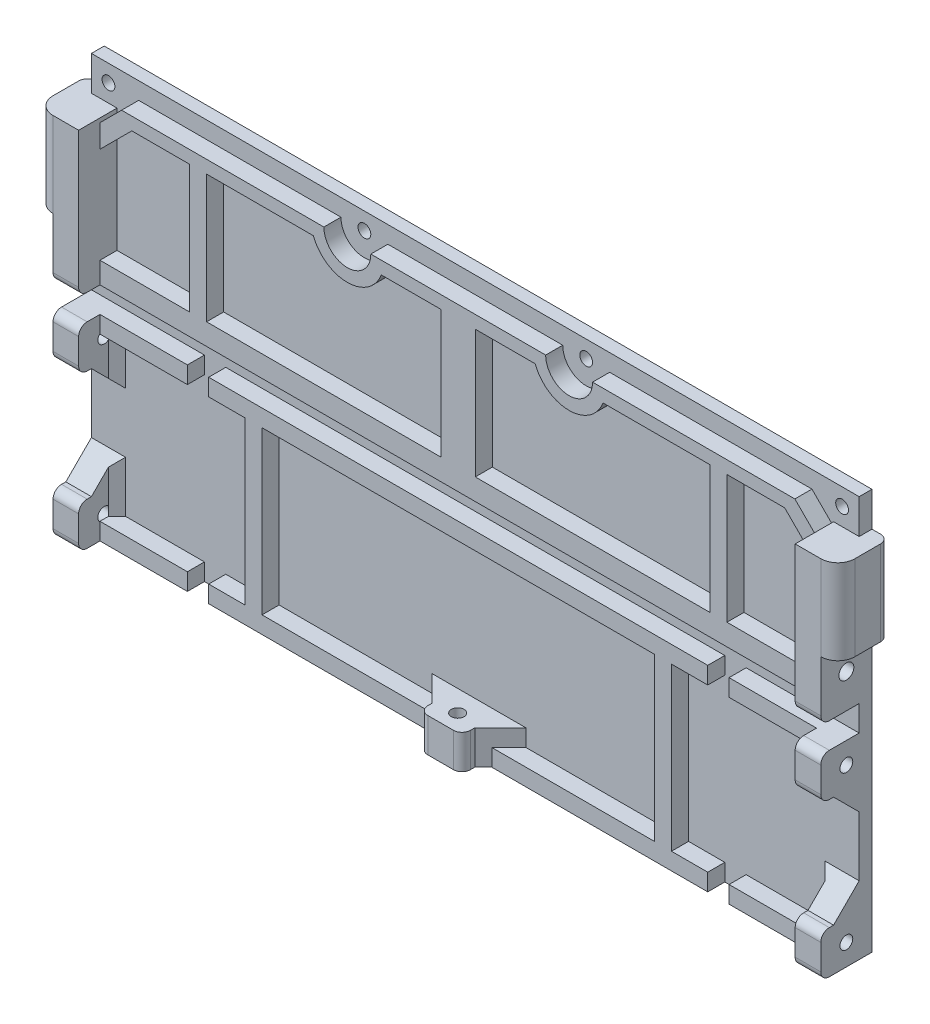
SolidWorks part; units mm, degrees
material "АБС-2020, черный"
ref_plane "Спереди" through (0, 0, 0) normal (0, 0, 1) x (1, 0, 0)
ref_plane "Сверху" through (0, 0, 0) normal (0, 1, 0) x (1, 0, 0)
ref_plane "Справа" through (0, 0, 0) normal (1, 0, 0) x (0, 0, -1)
other "Configuration Table"
sketch "Эскиз1" plane through (0, 0, 0) normal (0, 0, 1) x (1, 0, 0)
  line L1 (0, 0) -> (180, 0)
  line L2 (0, 0) -> (0, -94)
  line L3 (0, -94) -> (180, -94)
  line L4 (180, 0) -> (180, -94)
  dimension "D1" = 94
  dimension "D2" = 180
extrude "Бобышка-Вытянуть1" add sketch "Эскиз1" along normal blind 3
sketch "Эскиз2" plane through (0, 0, 3) normal (0, 0, 1) x (1, 0, 0)
  line L1 (0, -94) -> (6, -94)
  line L2 (0, -94) -> (0, -84)
  line L3 (0, -84) -> (6, -84)
  line L4 (6, -94) -> (6, -84)
  line L5 (180, -94) -> (174, -94)
  line L6 (180, -94) -> (180, -84)
  line L7 (180, -84) -> (174, -84)
  line L8 (174, -94) -> (174, -84)
  line L9 (0, -48) -> (6, -48)
  line L10 (0, -48) -> (0, -58)
  line L11 (0, -58) -> (6, -58)
  line L12 (6, -48) -> (6, -58)
  line L13 (180, -94) -> (180, 0) construction
  line L14 (180, -48) -> (174, -48)
  line L15 (180, -48) -> (180, -58)
  line L16 (180, -58) -> (174, -58)
  line L17 (174, -48) -> (174, -58)
  line L18 (0, -94) -> (180, -94) construction
  line L19 (180, 0) -> (0, 0) construction
  line L20 (180, -8.1) -> (174, -8.1)
  line L21 (180, -8.1) -> (180, -42)
  line L22 (180, -42) -> (174, -42)
  line L23 (174, -8.1) -> (174, -42)
  line L24 (0, -8.1) -> (6, -8.1)
  line L25 (0, -8.1) -> (0, -42)
  line L26 (0, -42) -> (6, -42)
  line L27 (6, -8.1) -> (6, -42)
  line L29 (85.876, -94) -> (95.876, -94)
  line L30 (85.876, -94) -> (85.876, -86)
  line L31 (85.876, -86) -> (95.876, -86)
  line L32 (95.876, -94) -> (95.876, -86)
  point P28 (3, -42)
  point P40 (90.876, -94)
  dimension "D1" = 10
  dimension "D2" = 6
  dimension "D3" = 10
  dimension "D4" = 6
  dimension "D5" = 46
  dimension "D6" = 6
  dimension "D7" = 6
  dimension "D9" = 10
  dimension "D10" = 10
  dimension "D11" = 6
  dimension "D12" = 8.1
  dimension "D13" = 8.1
  dimension "D14" = 6
  dimension "D15" = 10
  dimension "D16" = 5
  dimension "D17" = 8
extrude "Бобышка-Вытянуть2" add sketch "Эскиз2" along normal blind 9
chamfer "Фаска2" distance 6 angle 45 2 edges at (3, -58, 3) (177, -58, 3)
chamfer "Фаска1" distance 6 angle 45 2 edges at (3, -84, 3) (177, -84, 3)
sketch "Эскиз3" plane through (180, 0, 0) normal (1, 0, 0) x (0, 0, -1)
  line L0 (0, -94) -> (0, 0) construction
  line L1 (-12, -94) -> (0, -94) construction
  line L2 (-3, 0) -> (0, 0) construction
  circle A0 centre (-6, -89) radius 1.5
  circle A1 centre (-6, -53) radius 1.5
  circle A2 centre (-6, -34) radius 1.75
  dimension "D1" = 3
  dimension "D4" = 3
  dimension "D7" = 3.5
  dimension "D2" = 6
  dimension "D3" = 5
  dimension "D5" = 36
  dimension "D6" = 34
extrude "Вырез-Вытянуть1" cut sketch "Эскиз3" against normal blind 8
sketch "Эскиз4" plane through (0, 0, 3) normal (0, 0, 1) x (1, 0, 0)
  line L0 (0, -84) -> (0, -94) construction
  line L1 (180, -94) -> (180, -84) construction
  line L2 (180, 0) -> (0, 0) construction
  circle A0 centre (4, -4) radius 1.5
  circle A1 centre (176, -4) radius 1.5
  circle A2 centre (64, -4) radius 1.5
  circle A3 centre (116, -4) radius 1.5
  dimension "D7" = 3
  dimension "D4" = 3
  dimension "D5" = 3
  dimension "D1" = 4
  dimension "D2" = 4
  dimension "D3" = 4
  dimension "D6" = 60
  dimension "D8" = 60
extrude "Вырез-Вытянуть2" cut sketch "Эскиз4" against normal through all
sketch "Эскиз5" plane through (0, 0, 3) normal (0, 0, 1) x (1, 0, 0)
  line L2 (40, -52) -> (40, -90)
  line L4 (44, -52) -> (44, -90)
  line L5 (180, -78) -> (180, -64) construction
  line L7 (136, -52) -> (136, -90)
  line L9 (140, -52) -> (140, -90)
  line L10 (0, -64) -> (0, -78) construction
  line L11 (180, 0) -> (0, 0) construction
  line L13 (27, -4.5) -> (27, -37)
  line L15 (31, -4.5) -> (31, -37)
  line L18 (149, -4.5) -> (149, -37)
  line L20 (153, -4.5) -> (153, -37)
  line L21 (27, -4.5) -> (31, -4.5)
  line L22 (149, -4.5) -> (153, -4.5)
  line L23 (0, 0) -> (0, -8.1) construction
  line L24 (180, -48) -> (180, -42) construction
  line L25 (174, -8.1) -> (174, -42) construction
  line L26 (86, -4.5) -> (94, -4.5)
  line L27 (86, -4.5) -> (86, -37)
  line L29 (94, -4.5) -> (94, -37)
  line L31 (6, -42) -> (6, -37)
  line L32 (6, -37) -> (27, -37)
  line L33 (174, -42) -> (174, -37)
  line L34 (31, -37) -> (86, -37)
  line L35 (94, -37) -> (149, -37)
  line L36 (153, -37) -> (174, -37)
  line L37 (6, -42) -> (174, -42)
  line L39 (6, -48) -> (6, -52)
  line L40 (6, -52) -> (40, -52)
  line L41 (174, -48) -> (174, -52)
  line L42 (174, -48) -> (174, -58) construction
  line L43 (180, -48) -> (174, -48) construction
  line L44 (180, -48) -> (174, -48) construction
  line L45 (44, -52) -> (136, -52)
  line L46 (140, -52) -> (174, -52)
  line L47 (6, -48) -> (174, -48)
  line L48 (6, -90) -> (40, -90)
  line L49 (6, -94) -> (6, -84) construction
  line L50 (174, -84) -> (174, -94) construction
  line L51 (6, -90) -> (6, -94)
  line L53 (44, -90) -> (136, -90)
  line L54 (140, -90) -> (174, -90)
  line L55 (6, -94) -> (174, -94)
  line L56 (174, -94) -> (180, -94) construction
  line L57 (174, -94) -> (174, -90)
  dimension "D12" = 8
  dimension "D2" = 4
  dimension "D3" = 40
  dimension "D4" = 40
  dimension "D7" = 27
  dimension "D8" = 4
  dimension "D9" = 4.5
  dimension "D10" = 4
  dimension "D11" = 27
  dimension "D13" = 55
  dimension "D14" = 55
extrude "Бобышка-Вытянуть3" add sketch "Эскиз5" along normal blind 4
chamfer "Фаска3" distance 2 angle 45 4 edges at (174, -84, 3) (174, -58, 3) (6, -84, 3) (6, -58, 3)
sketch "Эскиз6" plane through (180, 0, 0) normal (1, 0, 0) x (0, 0, -1)
  line L0 (0, -94) -> (0, 0) construction
  line L1 (-12, -8.1) -> (0, -8.1)
  line L2 (-12, -8.1) -> (-12, -28)
  line L3 (-12, -28) -> (0, -28)
  line L4 (0, -8.1) -> (0, -28)
  line L5 (-3, 0) -> (0, 0) construction
  dimension "D1" = 28
  dimension "D2" = 8.1
extrude "Бобышка-Вытянуть4" add sketch "Эскиз6" along normal blind 4
fillet "Скругление1" radius 4 1 edges at (184, -18.05, 12)
sketch "Эскиз7" plane through (0, 0, 0) normal (-1, 0, 0) x (0, 0, 1)
  line L0 (12, -8.1) -> (12, -42) construction
  line L1 (0, -8.1) -> (12, -8.1)
  line L2 (0, -8.1) -> (0, -28)
  line L3 (0, -28) -> (12, -28)
  line L4 (12, -8.1) -> (12, -28)
  line L5 (3, 0) -> (0, 0) construction
  dimension "D1" = 28
extrude "Бобышка-Вытянуть5" add sketch "Эскиз7" along normal blind 4
fillet "Скругление2" radius 4 1 edges at (-4, -18.05, 12)
fillet "Скругление3" radius 2 2 edges at (184, -18.05, 0) (-4, -18.05, 0)
sketch "Эскиз8" plane through (0, -94, 0) normal (0, -1, 0) x (1, 0, 0)
  line L0 (97.876, 7) -> (136, 7) construction
  line L1 (85.876, 12) -> (85.876, 7) construction
  line L2 (0, 0) -> (180, 0) construction
  circle A0 centre (90.876, 8) radius 1.5
  dimension "D3" = 3
  dimension "D2" = 5
  dimension "D4" = 8
extrude "Вырез-Вытянуть3" cut sketch "Эскиз8" against normal blind 10
sketch "Эскиз9" plane through (0, 0, 0) normal (-1, 0, 0) x (0, 0, 1)
  line L0 (0, -28) -> (0, -94) construction
  line L1 (12, -94) -> (0, -94) construction
  circle A0 centre (6, -89) radius 1.5
  circle A1 centre (6, -53) radius 1.5
  dimension "D1" = 3
  dimension "D2" = 3
  dimension "D3" = 36
  dimension "D4" = 6
  dimension "D5" = 5
extrude "Вырез-Вытянуть4" cut sketch "Эскиз9" against normal blind 6
chamfer "Фаска4" distance 6 angle 45 2 edges at (95.876, -88, 3) (85.876, -88, 3)
fillet "Скругление4" radius 2 12 edges at (177, -84, 12) (3, -84, 12) (3, -42, 12) (3, -48, 12) (3, -58, 12) (3, -94, 12) (177, -42, 12) (177, -48, 12) (177, -58, 12) (85.876, -90, 12) (95.876, -90, 12) (177, -94, 12)
sketch "Эскиз10" plane through (0, 0, 3) normal (0, 0, 1) x (1, 0, 0)
  line L0 (11.0731, -4) -> (58.5, -4)
  line L1 (6, -14.4642) -> (13.4642, -7)
  line L2 (6, -37) -> (6, -8.1) construction
  line L3 (13.4642, -7) -> (56.047, -7)
  line L4 (166.5358, -7) -> (174, -14.4642)
  line L5 (174, -8.1) -> (174, -40) construction
  line L6 (174, -14.4642) -> (174, -9.0731)
  line L7 (174, -8.1) -> (174, -37) construction
  line L9 (174, -9.0731) -> (168.9269, -4)
  line L10 (6, -9.0731) -> (11.0731, -4)
  line L11 (69.5, -4) -> (110.5, -4)
  line L12 (71.953, -7) -> (108.047, -7)
  line L13 (6, -40) -> (6, -8.1) construction
  line L14 (123.953, -7) -> (166.5358, -7)
  line L15 (121.5, -4) -> (168.9269, -4)
  line L16 (6, -9.0731) -> (6, -14.4642)
  arc A0 (110.5, -4) -> (121.5, -4) centre (116, -4) ccw
  arc A1 (58.5, -4) -> (69.5, -4) centre (64, -4) ccw
  arc A4 (56.047, -7) -> (71.953, -7) centre (64, -4) ccw
  arc A5 (108.047, -7) -> (123.953, -7) centre (116, -4) ccw
  line M8 (6, -8.1) -> (6, -37)
  line M10 (27, -37) -> (27, -4.5)
  line M11 (27, -4.5) -> (31, -4.5)
  line M12 (31, -4.5) -> (31, -37)
  line M14 (86, -37) -> (86, -4.5)
  line M15 (86, -4.5) -> (94, -4.5)
  line M16 (94, -4.5) -> (94, -37)
  line M18 (149, -37) -> (149, -4.5)
  line M19 (149, -4.5) -> (153, -4.5)
  line M20 (153, -4.5) -> (153, -37)
  line M22 (174, -37) -> (174, -8.1)
  dimension "D1" = 17
  dimension "D5" = 17
  dimension "D2" = 3
  dimension "D3" = 45
  dimension "D4" = 45
extrude "Бобышка-Вытянуть6" add sketch "Эскиз10" along normal blind 4 contours L12 A5 L15 A0 L11 A1 L0 L10 L1 L3 A4 M8 M10 M11 M12 M14 M15 M16 | A5 L14 L4 L9 L15 M18 M19 M20 M22 region at (34.7866, -5.6833, 3)
sketch "Эскиз11" plane through (0, 0, 7) normal (0, 0, 1) x (1, 0, 0)
  line L0 (174, -48) -> (6, -48) construction
  line L1 (148.5, -48) -> (153.5, -48)
  line L2 (148.5, -48) -> (148.5, -94)
  line L3 (148.5, -94) -> (153.5, -94)
  line L4 (153.5, -48) -> (153.5, -94)
  line L5 (97.876, -94) -> (174, -94) construction
  line L6 (6, -94) -> (83.876, -94) construction
  line L7 (26.5, -48) -> (31.5, -48)
  line L8 (26.5, -48) -> (26.5, -94)
  line L9 (26.5, -94) -> (31.5, -94)
  line L10 (31.5, -48) -> (31.5, -94)
  line L11 (180, -78) -> (180, -64) construction
  line L12 (0, -86) -> (0, -92) construction
  dimension "D1" = 5
  dimension "D2" = 5
  dimension "D3" = 26.5
  dimension "D4" = 26.5
extrude "Вырез-Вытянуть5" cut sketch "Эскиз11" against normal blind 4
